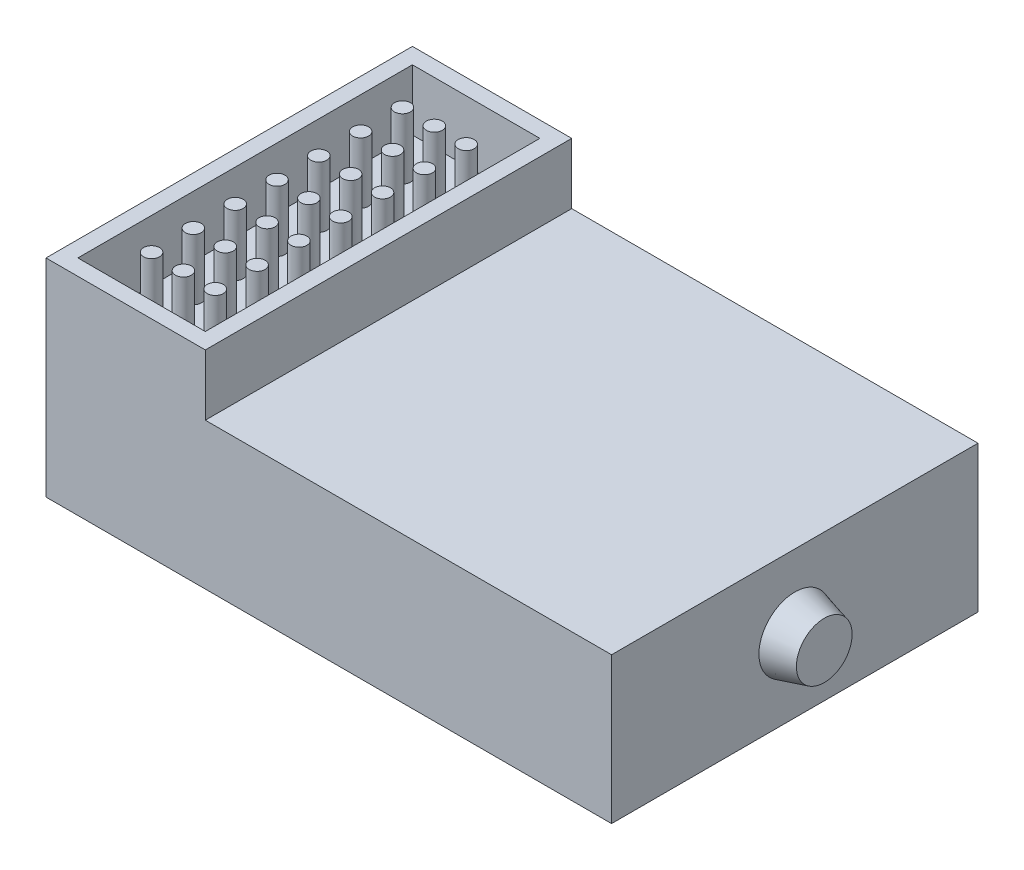
SolidWorks part; units mm, degrees
ref_plane "Front Plane" through (0, 0, 0) normal (0, 0, 1) x (1, 0, 0)
ref_plane "Top Plane" through (0, 0, 0) normal (0, 1, 0) x (1, 0, 0)
ref_plane "Right Plane" through (0, 0, 0) normal (1, 0, 0) x (0, 0, -1)
sketch "Sketch1" plane through (0, 0, 0) normal (0, 1, 0) x (1, 0, 0)
  line L1 (-17.75, -11.5) -> (17.75, -11.5)
  line L2 (-17.75, -11.5) -> (-17.75, 11.5)
  line L3 (-17.75, 11.5) -> (17.75, 11.5)
  line L4 (17.75, -11.5) -> (17.75, 11.5)
  line L5 (-17.75, -11.5) -> (17.75, 11.5) construction
  line L6 (-17.75, 11.5) -> (17.75, -11.5) construction
  point P0 (0, 0)
  dimension "D1" = 35.5
  dimension "D2" = 23
extrude "Boss-Extrude1" add sketch "Sketch1" along normal blind 9.18
sketch "Sketch2" plane through (0, 9.18, 0) normal (0, 1, 0) x (1, 0, 0)
  line L0 (-17.75, -11.5) -> (17.75, -11.5) construction
  line L1 (-17.75, 11.5) -> (-7.75, 11.5)
  line L2 (-17.75, 11.5) -> (-17.75, -11.5)
  line L3 (-17.75, -11.5) -> (-7.75, -11.5)
  line L4 (-7.75, 11.5) -> (-7.75, -11.5)
  line L5 (-17.75, 11.5) -> (-7.75, -11.5) construction
  line L6 (-17.75, -11.5) -> (-7.75, 11.5) construction
  line L11 (-16.75, 10.5) -> (-16.75, -10.5)
  line L12 (-16.75, -10.5) -> (-8.75, -10.5)
  line L13 (-8.75, 10.5) -> (-8.75, -10.5)
  line L14 (-16.75, 10.5) -> (-8.75, 10.5)
  point P4 (-12.75, 0)
  dimension "D1" = 10
  dimension "D2" = 1
extrude "Boss-Extrude2" add sketch "Sketch2" along normal blind 3.82
sketch "Sketch3" plane through (0, 9.18, 0) normal (0, 1, 0) x (1, 0, 0)
  line L0 (-14.75, 7.875) -> (-16.75, 7.875) construction
  line L1 (-8.75, 10.5) -> (-16.75, 10.5) construction
  line L2 (-16.75, 10.5) -> (-16.75, -10.5) construction
  line L3 (-14.75, 7.875) -> (-14.75, 10.5) construction
  line L4 (-14.75, 7.875) -> (-14.75, 5.25) construction
  line L5 (-12.75, 7.875) -> (-14.75, 7.875) construction
  circle A0 centre (-14.75, 7.875) radius 0.5
  circle A1 centre (-12.75, 7.875) radius 0.5
  circle A2 centre (-10.75, 7.875) radius 0.5
  circle A3 centre (-12.75, 5.25) radius 0.5
  circle A4 centre (-10.75, 5.25) radius 0.5
  circle A5 centre (-12.75, 2.625) radius 0.5
  circle A6 centre (-10.75, 2.625) radius 0.5
  circle A7 centre (-12.75, 0) radius 0.5
  circle A8 centre (-10.75, 0) radius 0.5
  circle A9 centre (-12.75, -2.625) radius 0.5
  circle A10 centre (-10.75, -2.625) radius 0.5
  circle A11 centre (-12.75, -5.25) radius 0.5
  circle A12 centre (-10.75, -5.25) radius 0.5
  circle A13 centre (-12.75, -7.875) radius 0.5
  circle A14 centre (-10.75, -7.875) radius 0.5
  circle A15 centre (-14.75, 5.25) radius 0.5
  circle A16 centre (-14.75, 2.625) radius 0.5
  circle A17 centre (-14.75, 0) radius 0.5
  circle A18 centre (-14.75, -2.625) radius 0.5
  circle A19 centre (-14.75, -5.25) radius 0.5
  circle A20 centre (-14.75, -7.875) radius 0.5
  point P2 (-14.75, 7.875)
  dimension "D3" = 1
  dimension "D1" = 2.625
  dimension "D2" = 2
  dimension "D4" = 3
  dimension "D5" = 7
extrude "Boss-Extrude3" add sketch "Sketch3" along normal up to surface (3.82 mm away) up to face at (-12.75, 13, 0)
sketch "Sketch5" plane through (0, 0, 0) normal (0, 0, 1) x (1, 0, 0)
  line L0 (17.75, 9.18) -> (17.75, 0) construction
  line L1 (17.75, 9.18) -> (17.75, 0) construction
  line L2 (17.75, 4.59) -> (19.6, 4.59)
  line L3 (19.6, 4.59) -> (19.6, 6.34)
  line L4 (19.6, 6.34) -> (17.75, 6.84)
  line L5 (17.75, 6.84) -> (17.75, 4.59)
  dimension "D1" = 1.85
  dimension "D2" = 2.25
  dimension "D3" = 1.75
revolve "Revolve1" add sketch "Sketch5" angle 360 about L2
